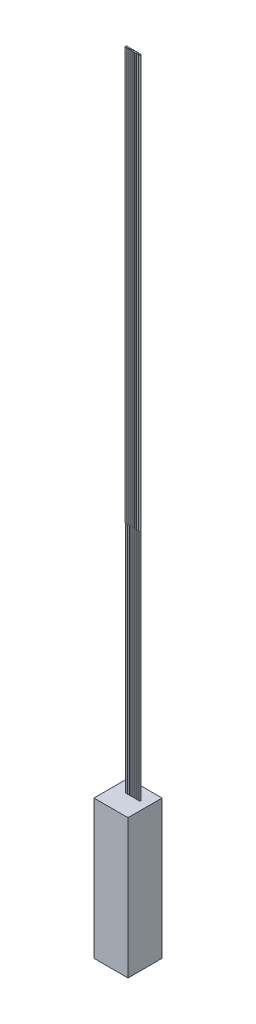
SolidWorks part; units mm, degrees
ref_plane "Front Plane" through (0, 0, 0) normal (0, 0, 1) x (1, 0, 0)
ref_plane "Top Plane" through (0, 0, 0) normal (0, 1, 0) x (1, 0, 0)
ref_plane "Right Plane" through (0, 0, 0) normal (1, 0, 0) x (0, 0, -1)
sketch "Fiber_Block_sketch" plane through (0, 0, 0) normal (0, 1, 0) x (1, 0, 0)
  line L1 (0, 0) -> (2.4786, 0)
  line L2 (0, 0) -> (0, -2.4786)
  line L3 (0, -2.4786) -> (2.4786, -2.4786)
  line L4 (2.4786, 0) -> (2.4786, -2.4786)
  dimension "D1" = 2.4786
extrude "Fiber_Block" add sketch "Fiber_Block_sketch" along normal blind 10.1
sketch "Fiber_Sketch" plane through (0, 10.1, 0) normal (0, 1, 0) x (1, 0, 0)
  line L0 (2.4786, 0) -> (0, 0) construction
  line L1 (0, 0) -> (0, -2.4786) construction
  circle A0 centre (0.85, -0.968) radius 0.05
  circle A1 centre (0.99, -0.968) radius 0.05
  circle A2 centre (1.13, -0.968) radius 0.05
  circle A3 centre (1.27, -0.968) radius 0.05
  circle A4 centre (1.41, -0.968) radius 0.05
  circle A5 centre (1.55, -0.968) radius 0.05
  circle A6 centre (1.69, -0.968) radius 0.05
  circle A7 centre (0.85, -0.968) radius 0.065
  circle A8 centre (0.99, -0.968) radius 0.065
  circle A9 centre (1.13, -0.968) radius 0.065
  circle A10 centre (1.27, -0.968) radius 0.065
  circle A11 centre (1.41, -0.968) radius 0.065
  circle A12 centre (1.55, -0.968) radius 0.065
  circle A13 centre (1.69, -0.968) radius 0.065
  circle A14 centre (1.83, -0.968) radius 0.065
  circle A15 centre (1.83, -0.968) radius 0.05
  point P21 (0, 0)
  dimension "D2" = 0.1
  dimension "D6" = 0.13
  dimension "D1" = 0.968
  dimension "D3" = 0.85
  dimension "D5" = 0.14
  dimension "D4" = 8
  dimension "D7" = 8
extrude "Fibers" add sketch "Fiber_Sketch" along normal blind 17 contours A15 | A6 | A5 | A4 | A3 | A2 | A0 | A1
extrude "Fiber_Shield" add sketch "Fiber_Sketch<3>" along normal blind 30 from surface separate body contours A7 A0 | A8 A1 | A9 A2 | A10 A3 | A11 A4 | A12 A5 | A13 A6 | A14 A15 | A15 | A6 | A5 | A4 | A3 | A0 | A1 | A2 region at (0.85, 10.1, 0.968) region at (0.99, 10.1, 0.968) region at (1.13, 10.1, 0.968) region at (1.27, 10.1, 0.968) region at (1.41, 10.1, 0.968) region at (1.55, 10.1, 0.968) region at (1.69, 10.1, 0.968) region at (0.7868, 10.1, 0.968) region at (0.9268, 10.1, 0.968) region at (1.0668, 10.1, 0.968) region at (1.2068, 10.1, 0.968) region at (1.3468, 10.1, 0.968) region at (1.4868, 10.1, 0.968) region at (1.6268, 10.1, 0.968) region at (1.7668, 10.1, 0.968) region at (1.83, 10.1, 0.968) starting at face at (1.69, 27.1, 1.018)
sketch "Fiber_Sketch<3>" plane through (0, 10.1, 0) normal (0, 1, 0) x (1, 0, 0) same geometry as "Fiber_Sketch"
